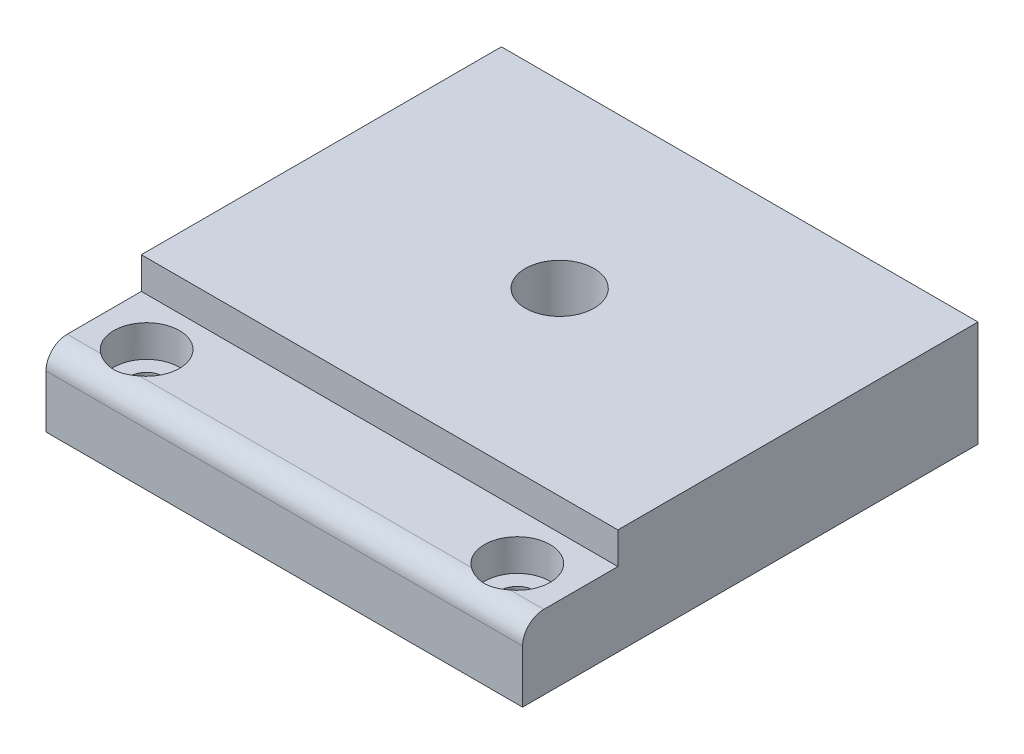
SolidWorks part; units mm, degrees
ref_plane "Plano frontal" through (0, 0, 0) normal (0, 0, 1) x (1, 0, 0)
ref_plane "Plano superior" through (0, 0, 0) normal (0, 1, 0) x (1, 0, 0)
ref_plane "Plano direito" through (0, 0, 0) normal (1, 0, 0) x (0, 0, -1)
sketch "Esboço1" plane through (0, 0, 0) normal (0, 0, 1) x (1, 0, 0)
  line L0 (-2.5, 0) -> (2.5, 0) construction
  line L1 (45, -1.5) -> (-45, -1.5)
  line L2 (45, -1.5) -> (45, 1.5)
  line L3 (45, 1.5) -> (-45, 1.5)
  line L4 (-45, -1.5) -> (-45, 1.5)
  line L5 (45, -1.5) -> (-45, 1.5) construction
  line L6 (45, 1.5) -> (-45, -1.5) construction
  point P0 (0, 0)
  point P11 (-45, 0)
  point P12 (0, 0)
  dimension "D1" = 90
  dimension "D2" = 3
  dimension "D4" = 5
extrude "Ressalto-extrusão1" add sketch "Esboço1" along normal blind 4
sketch "Esboço2" plane through (0, -1.5, 0) normal (0, -1, 0) x (1, 0, 0)
  line L0 (-45, 4) -> (45, 4) construction
  line L5 (0, 0) -> (45, 0)
  line L6 (0, 0) -> (0, 13)
  line L7 (0, 13) -> (45, 13)
  line L8 (45, 0) -> (45, 13)
  line L9 (40, 8.5) -> (45, 8.5) construction
  line L10 (5, 8.5) -> (0, 8.5) construction
  circle A0 centre (40, 8.5) radius 1.6
  circle A1 centre (5, 8.5) radius 1.6
  dimension "D2" = 3.2
  dimension "D1" = 9
  dimension "D3" = 4.5
  dimension "D4" = 5
extrude "Ressalto-extrusão3" add sketch "Esboço2" along normal blind 7
sketch "Esboço3" plane through (0, -1.5, 0) normal (0, 1, 0) x (1, 0, 0)
  circle A0 centre (5, -8.5) radius 3.1
  circle A1 centre (40, -8.5) radius 3.1
  dimension "D1" = 6.2
extrude "Corte-extrusão1" cut sketch "Esboço3" against normal blind 3 and the other way blind 10
fillet "Filete3" radius 2 1 edges at (22.5, -1.5, 13)
sketch "Esboço4" plane through (0, 0, 4) normal (0, 0, 1) x (1, 0, 0)
  line L1 (0, -1.5) -> (-45, -1.5)
  line L2 (0, -1.5) -> (0, 1.5)
  line L3 (0, 1.5) -> (-45, 1.5)
  line L4 (-45, -1.5) -> (-45, 1.5)
extrude "Corte-extrusão2" cut sketch "Esboço4" against normal through all
sketch "Esboço5" plane through (45, 0, 0) normal (1, 0, 0) x (0, 0, -1)
  line L0 (0, -8.5) -> (-13, -8.5) construction
  line L5 (0, 1.5) -> (30, 1.5)
  line L6 (0, 1.5) -> (0, -8.5)
  line L7 (0, -8.5) -> (30, -8.5)
  line L8 (30, 1.5) -> (30, -8.5)
  dimension "D1" = 30
extrude "Ressalto-extrusão4" add sketch "Esboço5" against normal up to surface (45 mm away) up to face at (0, -2.8694, 6.4877)
sketch "Esboço6" plane through (0, -8.5, 0) normal (0, -1, 0) x (1, 0, 0)
  line L0 (0, -30) -> (45, -30) construction
  line L1 (0, -30) -> (0, 4) construction
  line L2 (0, -30) -> (0, 4)
  circle A0 centre (22.5, -13) radius 3.25
  point P4 (22.5, -30)
  point P7 (0, -13)
  dimension "D1" = 6.5
extrude "Corte-extrusão3" cut sketch "Esboço6" against normal through all contours A0 region at (22.5, -8.5, -13)
sketch "Esboço7" plane through (0, -8.5, 0) normal (0, 1, 0) x (1, 0, 0)
  circle A0 centre (22.5, 13) radius 8.5
  dimension "D1" = 17
extrude "Corte-extrusão5" cut sketch "Esboço7" along normal blind 3
